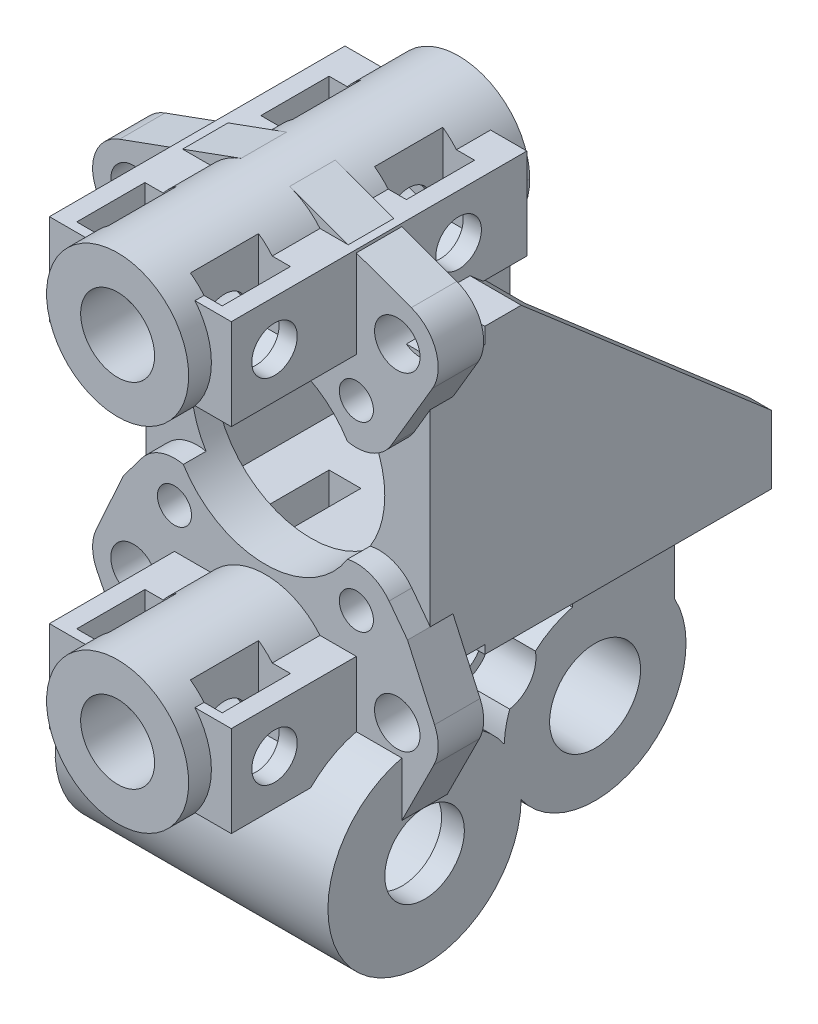
SolidWorks part; units mm, degrees
ref_plane "Front Plane" through (0, 0, 0) normal (0, 0, 1) x (1, 0, 0)
ref_plane "Top Plane" through (0, 0, 0) normal (0, 1, 0) x (1, 0, 0)
ref_plane "Right Plane" through (0, 0, 0) normal (1, 0, 0) x (0, 0, -1)
sketch "Sketch1" plane through (0, 0, 0) normal (0, 0, 1) x (1, 0, 0)
  line L0 (-62.844, 0) -> (62.844, 0) construction
  line L1 (-12, -3.5) -> (-10, -3.5)
  line L2 (-10, -3.5) -> (-10, -6.5)
  line L3 (-10, -6.5) -> (10, -6.5)
  line L4 (10, -6.5) -> (10, -3.5)
  line L5 (10, -3.5) -> (12, -3.5)
  line L6 (12, -3.5) -> (12, -8.5)
  line L7 (12, -8.5) -> (-12, -8.5)
  line L8 (-12, -8.5) -> (-12, -3.5)
  line L9 (0, 24.2806) -> (0, -63.9549) construction
  dimension "D1" = 3.5
  dimension "D2" = 2
  dimension "D3" = 20
  dimension "D4" = 2
  dimension "D5" = 6.5
revolve "Revolve1" add sketch "Sketch1" angle 360 about L0
ref_axis "Bearing Axis" through (12, 0, 0) along (-1, 0, 0)
sketch "Sketch2" plane through (0, 0, 0) normal (1, 0, 0) x (0, 0, -1)
  circle A0 centre (15, 4.5) radius 8
  circle A1 centre (15, 4.5) radius 4
  dimension "D1" = 8
  dimension "D2" = 16
  dimension "D3" = 15
  dimension "D4" = 4.5
extrude "Boss-Extrude1" add sketch "Sketch2" along normal up to surface and the other way up to surface up to face at (12, 0, 3.5) other way up to face at (-12, 0, 8.5)
ref_axis "Drive Shaft Axis" through (12, 4.5, -15) along (-1, 0, 0)
sketch "Sketch3" plane through (0, 0, 0) normal (0, 0, 1) x (1, 0, 0)
  line L0 (12, 0) -> (-12, 0) construction
  circle A2 centre (0, 10) radius 6.25
  circle A3 centre (0, 41) radius 6.25
  point P11 (0, 10)
  dimension "D1" = 31
  dimension "D3" = 12.5
  dimension "D2" = 10
extrude "Boss-Extrude2" add sketch "Sketch3" along normal blind 15 and the other way blind 15
sketch "Sketch4" plane through (0, 0, 0) normal (1, 0, 0) x (0, 0, -1)
  line L0 (30, 13) -> (0, 13)
  line L1 (0, 13) -> (0, 38)
  line L2 (0, 38) -> (8, 38)
  line L3 (8, 38) -> (30, 19)
  line L4 (30, 19) -> (30, 13)
  line L5 (-15, 47.25) -> (-15, 34.75) construction
  line L7 (-15, 16.25) -> (-15, 3.75) construction
  line L9 (-25.7365, 25.5) -> (29.2681, 25.5) construction
  point P8 (-15, 41)
  point P9 (-15, 10)
  dimension "D1" = 25
  dimension "D2" = 30
  dimension "D3" = 0
  dimension "D4" = 8
  dimension "D5" = 6
extrude "Boss-Extrude Motor Mount" add sketch "Sketch4" along normal mid plane 25
sketch "Sketch5" plane through (0, 0, 0) normal (1, 0, 0) x (0, 0, -1)
  line L0 (2, 15) -> (22, 15)
  line L1 (2, 36) -> (32, 36)
  line L2 (2, 36) -> (2, 15)
  line L3 (22, 15) -> (22, 11)
  line L4 (22, 11) -> (32, 11)
  line L5 (32, 11) -> (32, 36)
  line L6 (0, 13) -> (30, 13) construction
  line L7 (0, 38) -> (0, 13) construction
  dimension "D1" = 10
  dimension "D2" = 4
  dimension "D3" = 30
  dimension "D4" = 21
  dimension "D5" = 2
  dimension "D6" = 2
extrude "Cut-Extrude1" cut sketch "Sketch5" against normal mid plane 21
sketch "Sketch6" plane through (0, 0, -2) normal (0, 0, -1) x (-1, 0, 0)
  line L0 (0, 36) -> (0, 15) construction
  line L2 (10.5, 15) -> (-10.5, 15) construction
  line L3 (-10.5, 25.5) -> (10.5, 25.5) construction
  line L4 (-10.5, 36) -> (-10.5, 15) construction
  line L5 (10.5, 36) -> (10.5, 15) construction
  line L6 (-10.5, 36) -> (-10.5, 15) construction
  circle A0 centre (0, 25.5) radius 8.5
  circle A2 centre (8, 33.5) radius 1.5
  circle A3 centre (-8, 33.5) radius 1.5
  circle A4 centre (8, 17.5) radius 1.5
  circle A5 centre (-8, 17.5) radius 1.5
  dimension "D1" = 17
  dimension "D2" = 3
  dimension "D3" = 16
  dimension "D4" = 16
extrude "Cut-Extrude2" cut sketch "Sketch6" against normal up to next
ref_axis "Motor Shaft Axis" [suppressed] through (-10, -13.5, 20) along (0, 0, -1)
sketch "Sketch9" plane through (0, 0, 0) normal (0, 0, 1) x (1, 0, 0)
  line L0 (-4.8023, 14) -> (-8, 14)
  line L1 (-8, 14) -> (-8, 6)
  line L2 (-8, 6) -> (-4.8023, 6)
  line L3 (4.8023, 6) -> (8, 6)
  line L4 (8, 6) -> (8, 14)
  line L5 (8, 14) -> (4.8023, 14)
  line L6 (-7.4398, 10) -> (9.8164, 10) construction
  line L7 (0, 5.766) -> (0, 49.3581) construction
  line L8 (-4.8023, 45) -> (-8, 45)
  line L9 (-8, 45) -> (-8, 37)
  line L10 (-8, 37) -> (-4.8023, 37)
  line L11 (4.8023, 45) -> (8, 45)
  line L12 (8, 45) -> (8, 37)
  line L13 (8, 37) -> (4.8023, 37)
  line L14 (-12.1178, 41) -> (12.8795, 41) construction
  circle A3 centre (0, 41) radius 6.25 construction
  arc A5 (-4.8023, 14) -> (-4.8023, 6) centre (0, 10) ccw
  arc A6 (-4.8023, 45) -> (-4.8023, 37) centre (0, 41) ccw
  arc A7 (4.8023, 45) -> (4.8023, 37) centre (0, 41) cw
  arc A8 (4.8023, 14) -> (4.8023, 6) centre (0, 10) cw
  circle A9 centre (0, 10) radius 6.25 construction
  dimension "D1" = 8
  dimension "D2" = 8
  dimension "D3" = 8
  dimension "D4" = 8
extrude "Boss-Extrude Grub Screw Mounts" add sketch "Sketch9" along normal offset from surface 2 and the other way offset from surface 2 up to face at (6.25, 10, 15) other way up to face at (0, 41.625, -15)
sketch "Sketch8" plane through (0, 0, 0) normal (0, 0, 1) x (1, 0, 0)
  line L0 (-14.8805, 12.2326) -> (-12.5, 17.5)
  line L1 (-12.5, 38) -> (-12.5, 13) construction
  line L2 (-12.8307, 42.9831) -> (-2.1367, 46.8734)
  line L3 (12.8307, 42.9831) -> (2.1367, 46.8734)
  line L4 (-10.5, 36) -> (10.5, 36) construction
  line L5 (-14.82, 9.1401) -> (-12, 3.5)
  line L6 (12.5, 38) -> (12.5, 13) construction
  line L7 (0, 30.0704) -> (0, -18.0127) construction
  line L8 (12.5, 17.5) -> (14.8805, 12.2326)
  line L9 (-8, 14) -> (-8, 6) construction
  line L10 (-10.88, 19.66) -> (-12.5, 17.5)
  line L11 (14.82, 9.1401) -> (12, 3.5)
  line L12 (8, 37) -> (8, 45) construction
  line L13 (-11.1003, 31.6703) -> (-14.7003, 37.7703)
  line L14 (10.88, 19.66) -> (12.5, 17.5)
  line L15 (11.1003, 31.6703) -> (14.7003, 37.7703)
  line L17 (12, -8.5) -> (12, 8.5) construction
  line L18 (-12, 8.5) -> (-12, -8.5) construction
  line L20 (12, 3.5) -> (-12, 3.5)
  line L21 (-14.7591, 10.75) -> (16.9657, 10.75) construction
  line L22 (12.5, 13) -> (8, 13) construction
  line L23 (12, 8.5) -> (8, 8.5) construction
  circle A0 centre (-11.6, 10.75) radius 2
  circle A1 centre (11.6, 10.75) radius 2
  circle A2 centre (0, 41) radius 6.25 construction
  arc A3 (14.8805, 12.2326) -> (14.82, 9.1401) centre (11.6, 10.75) cw
  circle A4 centre (-11.6, 39.6) radius 2
  circle A5 centre (11.6, 39.6) radius 2
  arc A6 (-10.88, 19.66) -> (-7.2201, 21.0145) centre (-8, 17.5) cw
  arc A7 (-7.2201, 21.0145) -> (7.2201, 21.0145) centre (0, 25.5) ccw
  arc A8 (7.2201, 21.0145) -> (10.88, 19.66) centre (8, 17.5) cw
  circle A9 centre (0, 25.5) radius 8.5 construction
  circle A10 centre (-8, 17.5) radius 1.5
  circle A11 centre (8, 17.5) radius 1.5
  circle A12 centre (8, 17.5) radius 1.5 construction
  circle A13 centre (-8, 17.5) radius 1.5 construction
  circle A14 centre (0, 10) radius 6.25
  circle A15 centre (0, 10) radius 6.25 construction
  arc A16 (-12.8307, 42.9831) -> (-14.7003, 37.7703) centre (-11.6, 39.6) ccw
  arc A17 (12.8307, 42.9831) -> (14.7003, 37.7703) centre (11.6, 39.6) cw
  arc A20 (2.1367, 46.8734) -> (-2.1367, 46.8734) centre (0, 41) ccw
  arc A21 (-7.2201, 29.9855) -> (7.2201, 29.9855) centre (0, 25.5) cw
  arc A22 (-7.2201, 29.9855) -> (-11.1003, 31.6703) centre (-8, 33.5) cw
  arc A23 (7.2201, 29.9855) -> (11.1003, 31.6703) centre (8, 33.5) ccw
  circle A24 centre (-8, 33.5) radius 1.5
  circle A25 centre (8, 33.5) radius 1.5
  circle A26 centre (8, 33.5) radius 1.5 construction
  circle A27 centre (-8, 33.5) radius 1.5 construction
  arc A28 (-14.8805, 12.2326) -> (-14.82, 9.1401) centre (-11.6, 10.75) ccw
  dimension "D1" = 3.6
  dimension "D2" = 3.6
  dimension "D4" = 3.6
  dimension "D6" = 3.6
  dimension "D3" = 3.6
  dimension "D5" = 4
extrude "Boss-Extrude Flange" add sketch "Sketch8" along normal mid plane 4
sketch "Sketch10" plane through (0, 0, 0) normal (-1, 0, 0) x (0, 0, 1)
  line L0 (13, 41) -> (-13, 41) construction
  line L1 (13, 45) -> (13, 37) construction
  line L2 (-13, 37) -> (-13, 45) construction
  line L3 (13, 10) -> (-12.4618, 10) construction
  line L4 (13, 14) -> (13, 6) construction
  line L5 (-13, 12.246) -> (-13, 13) construction
  circle A0 centre (9.2, 10) radius 2
  circle A1 centre (-7, 10) radius 2
  circle A2 centre (9.2, 41) radius 2
  circle A3 centre (-7, 41) radius 2
  dimension "D1" = 4
  dimension "D2" = 6
  dimension "D3" = 3.8
extrude "Cut-Extrude3" cut sketch "Sketch10" against normal through all and the other way through all
ref_plane "Right Nut Plane" through (5, 0, 0) normal (1, 0, 0) x (0, 0, -1)
sketch "Sketch11" plane through (5, 0, 0) normal (1, 0, 0) x (0, 0, -1)
  line L0 (-12.2, 42.7321) -> (-12.2, 48.5938)
  line L1 (-9.2, 44.4641) -> (-12.2, 42.7321) construction
  line L2 (-12.2, 42.7321) -> (-12.2, 39.2679)
  line L3 (-12.2, 39.2679) -> (-9.2, 37.5359)
  line L4 (-9.2, 37.5359) -> (-6.2, 39.2679)
  line L5 (-6.2, 39.2679) -> (-6.2, 42.7321)
  line L6 (-6.2, 42.7321) -> (-9.2, 44.4641) construction
  line L7 (7, 44.4641) -> (4, 42.7321) construction
  line L8 (4, 42.7321) -> (4, 39.2679)
  line L9 (4, 39.2679) -> (7, 37.5359)
  line L10 (7, 37.5359) -> (10, 39.2679)
  line L11 (10, 39.2679) -> (10, 42.7321)
  line L12 (10, 42.7321) -> (7, 44.4641) construction
  line L13 (-9.2, 13.4641) -> (-12.2, 11.7321) construction
  line L14 (-12.2, 11.7321) -> (-12.2, 8.2679)
  line L15 (-12.2, 8.2679) -> (-9.2, 6.5359)
  line L16 (-9.2, 6.5359) -> (-6.2, 8.2679)
  line L17 (-6.2, 8.2679) -> (-6.2, 11.7321)
  line L18 (-6.2, 11.7321) -> (-9.2, 13.4641) construction
  line L19 (7, 13.4641) -> (4, 11.7321) construction
  line L20 (4, 11.7321) -> (4, 8.2679)
  line L21 (4, 8.2679) -> (7, 6.5359)
  line L22 (7, 6.5359) -> (10, 8.2679)
  line L23 (10, 8.2679) -> (10, 11.7321)
  line L24 (10, 11.7321) -> (7, 13.4641) construction
  line L25 (-12.2, 48.5938) -> (-6.2, 48.5938)
  line L26 (-6.2, 48.5938) -> (-6.2, 42.7321)
  line L27 (4, 42.7321) -> (4, 50.4232)
  line L28 (4, 50.4232) -> (10, 50.4232)
  line L29 (10, 50.4232) -> (10, 42.7321)
  line L30 (-12.2, 11.7321) -> (-12.2, 16.25)
  line L31 (-12.2, 16.25) -> (-6.2, 16.25)
  line L32 (-6.2, 16.25) -> (-6.2, 11.7321)
  line L33 (4, 11.7321) -> (4, 15)
  line L34 (4, 15) -> (10, 15)
  line L35 (10, 15) -> (10, 11.7321)
  line L36 (-2, 16.25) -> (-15, 16.25) construction
  line L39 (2, 15) -> (22, 15) construction
  circle A0 centre (-9.2, 41) radius 3 construction
  circle A1 centre (7, 41) radius 3 construction
  circle A2 centre (-9.2, 10) radius 3 construction
  circle A3 centre (7, 10) radius 3 construction
  dimension "D1" = 6
extrude "Cut-Extrude4" cut sketch "Sketch11" against normal mid plane 2.8
ref_plane "Left Nut Plane" through (-5, 0, 0) normal (1, 0, 0) x (0, 0, -1)
sketch "Sketch12" plane through (-5, 0, 0) normal (1, 0, 0) x (0, 0, -1)
  line L0 (-12.2, 42.7321) -> (-12.2, 47.25)
  line L1 (-9.2, 44.4641) -> (-12.2, 42.7321) construction
  line L2 (-12.2, 42.7321) -> (-12.2, 39.2679)
  line L3 (-12.2, 39.2679) -> (-9.2, 37.5359)
  line L4 (-9.2, 37.5359) -> (-6.2, 39.2679)
  line L5 (-6.2, 39.2679) -> (-6.2, 42.7321)
  line L6 (-6.2, 42.7321) -> (-9.2, 44.4641) construction
  line L7 (7, 44.4641) -> (4, 42.7321) construction
  line L8 (4, 42.7321) -> (4, 39.2679)
  line L9 (4, 39.2679) -> (7, 37.5359)
  line L10 (7, 37.5359) -> (10, 39.2679)
  line L11 (10, 39.2679) -> (10, 42.7321)
  line L12 (10, 42.7321) -> (7, 44.4641) construction
  line L13 (-9.2, 13.4641) -> (-12.2, 11.7321) construction
  line L14 (-12.2, 11.7321) -> (-12.2, 8.2679)
  line L15 (-12.2, 8.2679) -> (-9.2, 6.5359)
  line L16 (-9.2, 6.5359) -> (-6.2, 8.2679)
  line L17 (-6.2, 8.2679) -> (-6.2, 11.7321)
  line L18 (-6.2, 11.7321) -> (-9.2, 13.4641) construction
  line L19 (7, 13.4641) -> (4, 11.7321) construction
  line L20 (4, 11.7321) -> (4, 8.2679)
  line L21 (4, 8.2679) -> (7, 6.5359)
  line L22 (7, 6.5359) -> (10, 8.2679)
  line L23 (10, 8.2679) -> (10, 11.7321)
  line L24 (10, 11.7321) -> (7, 13.4641) construction
  line L25 (-12.2, 47.25) -> (-6.2, 47.25)
  line L26 (-6.2, 47.25) -> (-6.2, 42.7321)
  line L27 (4, 42.7321) -> (4, 47.25)
  line L28 (4, 47.25) -> (10, 47.25)
  line L29 (10, 47.25) -> (10, 42.7321)
  line L30 (-12.2, 11.7321) -> (-12.2, 16.25)
  line L31 (-12.2, 16.25) -> (-6.2, 16.25)
  line L32 (-6.2, 16.25) -> (-6.2, 11.7321)
  line L33 (4, 11.7321) -> (4, 15)
  line L34 (4, 15) -> (10, 15)
  line L35 (10, 15) -> (10, 11.7321)
  line L37 (15, 47.25) -> (-15, 47.25) construction
  line L38 (-2, 16.25) -> (-15, 16.25) construction
  line L40 (2, 15) -> (22, 15) construction
  circle A0 centre (-9.2, 41) radius 3 construction
  circle A1 centre (7, 41) radius 3 construction
  circle A2 centre (-9.2, 10) radius 3 construction
  circle A3 centre (7, 10) radius 3 construction
  circle A4 centre (-9.2, 10) radius 2 construction
  arc A5 (8.9876, 9.7774) -> (7.9196, 8.224) centre (7, 10) ccw construction
  circle A6 centre (-9.2, 41) radius 2 construction
  circle A7 centre (7, 41) radius 2 construction
  dimension "D1" = 6
extrude "Cut-Extrude5" cut sketch "Sketch12" against normal mid plane 2.8
sketch "Sketch14" plane through (0, 0, 0) normal (1, 0, 0) x (0, 0, -1)
  line L0 (22, 8.373) -> (22, 15)
  line L1 (22, 15) -> (13, 15)
  line L2 (13, 15) -> (13, 12.246)
  line L3 (13, 12.246) -> (13, 13) construction
  arc A0 (22, 8.373) -> (13, 12.246) centre (15, 4.5) ccw
  arc A1 (8.4985, -0.1615) -> (8.9876, 9.7774) centre (15, 4.5) ccw construction
extrude "Boss-Extrude6" add sketch "Sketch14" against normal up to surface and the other way up to surface up to face at (-12, 3.8675, -3.4913) other way up to face at (12, 3.8675, -3.4913)
ref_plane "Lead Nut Plane" through (0, 0, 0) normal (1, 0, 0) x (0, 0, -1)
sketch "Sketch15" plane through (0, 0, 0) normal (1, 0, 0) x (0, 0, -1)
  line L0 (17.9445, 9.6) -> (23, 9.6)
  line L1 (17.9445, -0.6) -> (20.889, 4.5) construction
  line L2 (20.889, 4.5) -> (17.9445, 9.6) construction
  line L3 (17.9445, 9.6) -> (12.0555, 9.6)
  line L4 (12.0555, 9.6) -> (9.111, 4.5)
  line L5 (9.111, 4.5) -> (12.0555, -0.6)
  line L6 (12.0555, -0.6) -> (17.9445, -0.6)
  line L7 (23, 9.6) -> (23, -0.6)
  line L8 (23, -0.6) -> (17.9445, -0.6)
  circle A0 centre (15, 4.5) radius 5.1 construction
  arc A1 (8.4985, -0.1615) -> (22, 8.373) centre (15, 4.5) ccw construction
  dimension "D1" = 10.2
extrude "Cut-Extrude Lead Nut" cut sketch "Sketch15" against normal mid plane 5.5
sketch "Sketch16" plane through (8, 0, 0) normal (1, 0, 0) x (0, 0, -1)
  circle A0 centre (7, 10) radius 2.8
  dimension "D1" = 5.6
extrude "Cut-Extrude7" cut sketch "Sketch16" along normal through all
sketch "Sketch17" plane through (-8, 0, 0) normal (-1, 0, 0) x (0, 0, 1)
  circle A0 centre (-7, 10) radius 2.8
  dimension "D1" = 5.6
extrude "Cut-Extrude8" cut sketch "Sketch17" along normal through all
sketch "Sketch18" plane through (0, 0, -2) normal (0, 0, -1) x (-1, 0, 0)
  line L1 (-15.0641, 39.6) -> (-13.3321, 36.6)
  line L2 (-13.3321, 36.6) -> (-9.8679, 36.6)
  line L3 (-9.8679, 36.6) -> (-8.1359, 39.6)
  line L4 (-8.1359, 39.6) -> (-9.8679, 42.6)
  line L5 (-9.8679, 42.6) -> (-13.3321, 42.6)
  line L6 (-13.3321, 42.6) -> (-15.0641, 39.6)
  line L7 (15.0641, 39.6) -> (13.3321, 42.6)
  line L8 (13.3321, 42.6) -> (9.8679, 42.6)
  line L9 (9.8679, 42.6) -> (8.1359, 39.6)
  line L10 (8.1359, 39.6) -> (9.8679, 36.6)
  line L11 (9.8679, 36.6) -> (13.3321, 36.6)
  line L12 (13.3321, 36.6) -> (15.0641, 39.6)
  line L13 (15.0641, 10.75) -> (13.3321, 13.75)
  line L14 (13.3321, 13.75) -> (9.8679, 13.75)
  line L15 (9.8679, 13.75) -> (8.1359, 10.75)
  line L16 (8.1359, 10.75) -> (9.8679, 7.75)
  line L17 (9.8679, 7.75) -> (13.3321, 7.75)
  line L18 (13.3321, 7.75) -> (15.0641, 10.75)
  line L19 (-15.0641, 10.75) -> (-13.3321, 7.75)
  line L20 (-13.3321, 7.75) -> (-9.8679, 7.75)
  line L21 (-9.8679, 7.75) -> (-8.1359, 10.75)
  line L22 (-8.1359, 10.75) -> (-9.8679, 13.75)
  line L23 (-9.8679, 13.75) -> (-13.3321, 13.75)
  line L24 (-13.3321, 13.75) -> (-15.0641, 10.75)
  circle A0 centre (-11.6, 39.6) radius 3 construction
  circle A1 centre (11.6, 39.6) radius 3 construction
  circle A2 centre (11.6, 10.75) radius 3 construction
  circle A3 centre (-11.6, 10.75) radius 3 construction
  dimension "D1" = 6
extrude "Cut-Extrude9" cut sketch "Sketch18" against normal blind 1 and the other way blind 2.8
sketch "Sketch19" plane through (0, 0, 15) normal (0, 0, 1) x (1, 0, 0)
  circle A0 centre (0, 10) radius 3.25
  circle A1 centre (0, 41) radius 3.25
  circle A4 centre (0, 41) radius 6.25 construction
  circle A5 centre (0, 10) radius 6.25 construction
  dimension "D1" = 6.5
extrude "Cut-Extrude10" cut sketch "Sketch19" against normal blind 27
sketch "Sketch20" plane through (0, 0, 0) normal (1, 0, 0) x (0, 0, -1)
  circle A0 centre (15, 4.5) radius 4
  circle A1 centre (15, 4.5) radius 4 construction
extrude "Cut-Extrude11" cut sketch "Sketch20" against normal through all and the other way through all
sketch "Sketch23" plane through (0, 0, 0) normal (1, 0, 0) x (0, 0, -1)
  circle A0 centre (0, 0) radius 6.5
  arc A1 (-2, 6.1847) -> (2, 6.1847) centre (0, 0) ccw construction
extrude "Cut-Extrude12" cut sketch "Sketch23" against normal up to surface (10 mm away) and the other way up to surface (10 mm away) up to face at (-10, 1.6974, 0.5833) other way up to face at (10, 1.6974, 0.5833)
sketch "Sketch24" plane through (0, 0, 2) normal (0, 0, 1) x (1, 0, 0)
  circle A0 centre (-11.6, 10.75) radius 3.6
  arc A2 (-14.8805, 12.2326) -> (-14.82, 9.1401) centre (-11.6, 10.75) ccw construction
extrude "Cut-Extrude13" cut sketch "Sketch24" along normal through all
split "Split1" [suppressed] bodies to split 124
